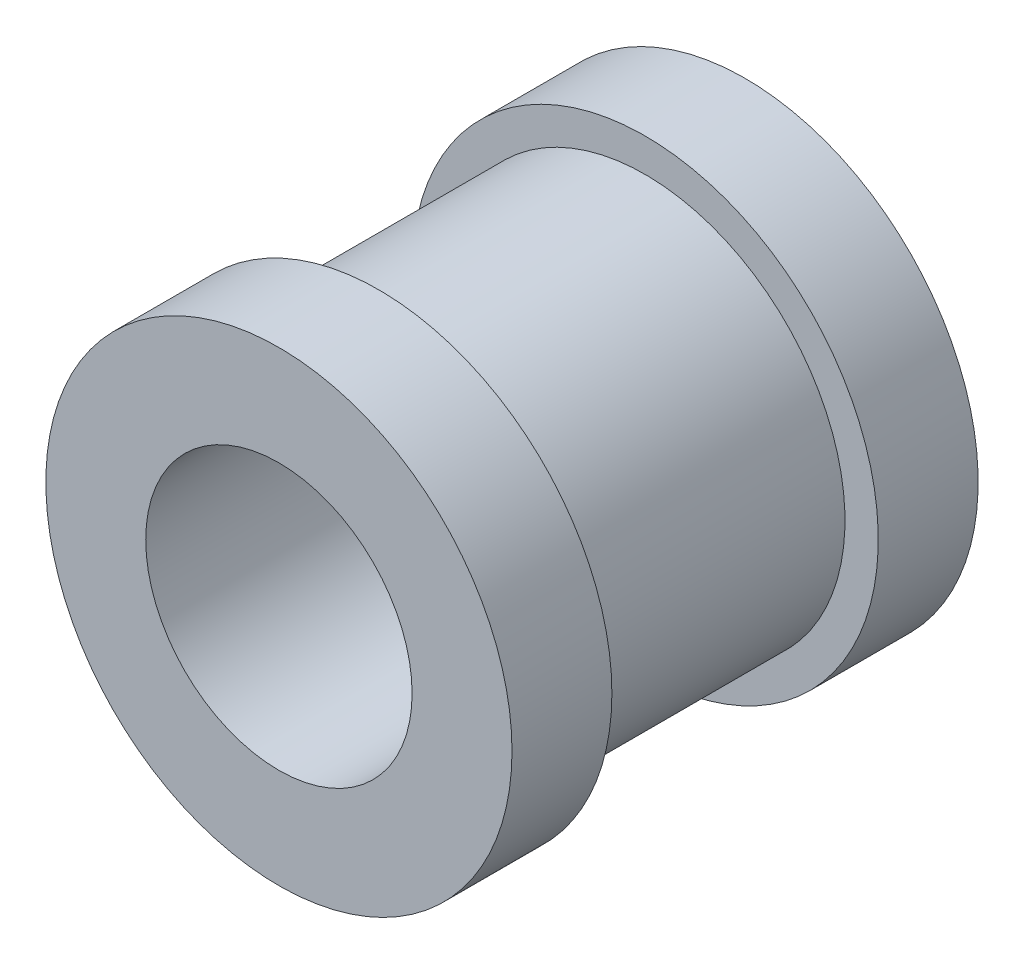
SolidWorks part; units mm, degrees
ref_plane "Front Plane" through (0, 0, 0) normal (0, 0, 1) x (1, 0, 0)
ref_plane "Top Plane" through (0, 0, 0) normal (0, 1, 0) x (1, 0, 0)
ref_plane "Right Plane" through (0, 0, 0) normal (1, 0, 0) x (0, 0, -1)
sketch "Sketch1" plane through (0, 0, 0) normal (0, 0, 1) x (1, 0, 0)
  circle A0 centre (0, 0) radius 6
  circle A1 centre (0, 0) radius 4
  dimension "D1" = 12
  dimension "D2" = 8
extrude "Boss-Extrude1" add sketch "Sketch1" along normal mid plane 14
sketch "Sketch2" plane through (0, 0, -7) normal (0, 0, -1) x (-1, 0, 0)
  circle A0 centre (0, 0) radius 7
  circle A1 centre (0, 0) radius 6
  dimension "D1" = 14
extrude "Boss-Extrude2" add sketch "Sketch2" against normal blind 3
sketch "Sketch3" plane through (0, 0, 7) normal (0, 0, 1) x (1, 0, 0)
  circle A0 centre (0, 0) radius 7
  circle A1 centre (0, 0) radius 6
extrude "Boss-Extrude3" add sketch "Sketch3" against normal blind 3
